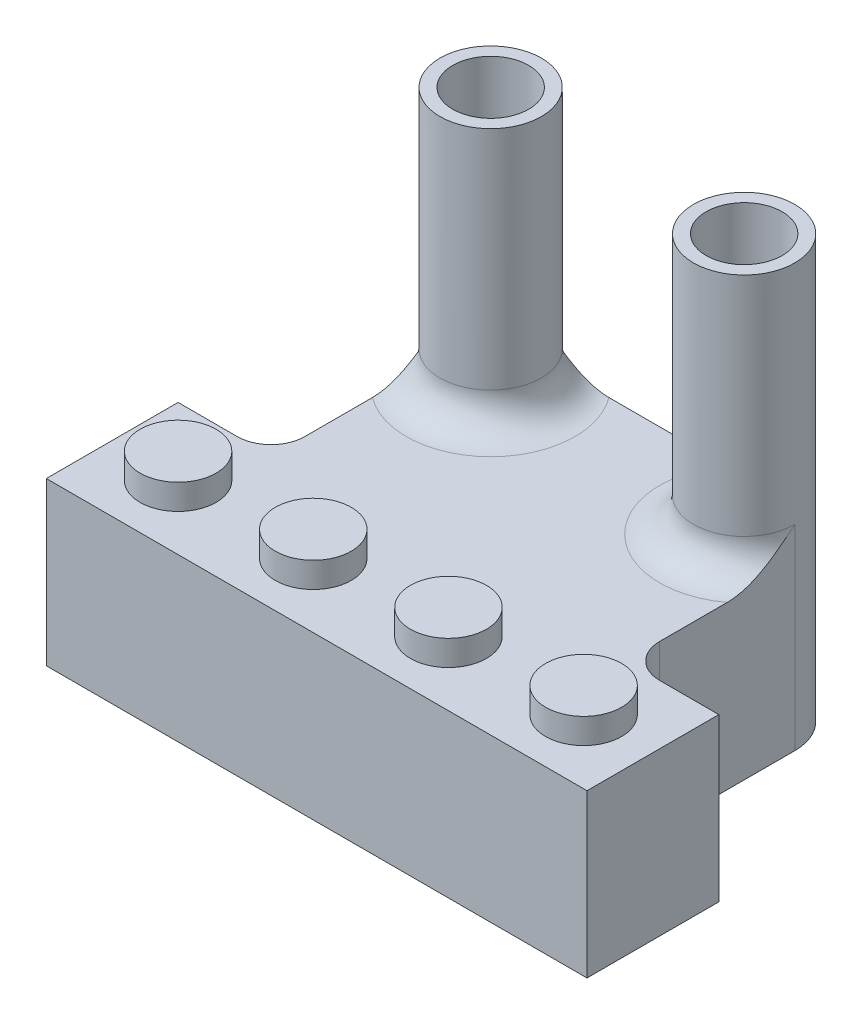
SolidWorks part; units mm, degrees
ref_plane "Front Plane" through (0, 0, 0) normal (0, 0, 1) x (1, 0, 0)
ref_plane "Top Plane" through (0, 0, 0) normal (0, 1, 0) x (1, 0, 0)
ref_plane "Right Plane" through (0, 0, 0) normal (1, 0, 0) x (0, 0, -1)
sketch "Sketch1" plane through (0, -0.3266, 0) normal (0, 1, 0) x (1, 0, 0)
  line L0 (236.8738, 42.5699) -> (268.8738, 42.5699)
  line L2 (236.8738, 50.3699) -> (236.8738, 42.5699)
  line L3 (236.8738, 50.3699) -> (268.8738, 50.3699)
  line L4 (268.8738, 34.3699) -> (268.8738, 50.3699)
  line L5 (268.8738, 50.3699) -> (236.8738, 50.3699)
  line L6 (236.8738, 50.3699) -> (236.8738, 34.3699)
  line L7 (236.8738, 34.3699) -> (268.8738, 34.3699)
  line L8 (268.8738, 34.3699) -> (268.8738, 50.3699) construction
  line L9 (268.8738, 50.3699) -> (236.8738, 50.3699) construction
  line L10 (236.8738, 50.3699) -> (236.8738, 34.3699) construction
  line L11 (236.8738, 34.3699) -> (268.8738, 34.3699) construction
  line L12 (268.8738, 50.3699) -> (268.8738, 42.5699)
  line L13 (242.3738, 50.3699) -> (242.3738, 61.3699)
  line L14 (244.3738, 63.3699) -> (261.3738, 63.3699)
  line L15 (263.3738, 61.3699) -> (263.3738, 50.3699)
  arc A0 (260.3738, 58.8199) -> (260.3738, 61.9199) centre (260.3738, 60.3699) ccw construction
  arc A1 (245.3738, 58.8199) -> (245.3738, 61.9199) centre (245.3738, 60.3699) ccw construction
  arc A2 (260.3738, 58.8199) -> (260.3738, 61.9199) centre (260.3738, 60.3699) ccw construction
  arc A3 (245.3738, 58.8199) -> (245.3738, 61.9199) centre (245.3738, 60.3699) ccw construction
  circle A12 centre (240.8738, 46.3699) radius 2.25
  circle A13 centre (248.8738, 46.3699) radius 2.25
  circle A14 centre (245.3738, 60.3699) radius 2.25
  circle A15 centre (260.3738, 60.3699) radius 2.25
  arc A16 (261.3738, 63.3699) -> (263.3738, 61.3699) centre (261.3738, 61.3699) cw
  arc A17 (242.3738, 61.3699) -> (244.3738, 63.3699) centre (244.3738, 61.3699) cw
  circle A18 centre (260.3738, 60.3699) radius 3
  circle A19 centre (245.3738, 60.3699) radius 3
  circle A20 centre (264.8738, 46.3699) radius 2.4 construction
  circle A21 centre (256.8738, 46.3699) radius 2.4 construction
  circle A22 centre (248.8738, 46.3699) radius 2.4 construction
  circle A23 centre (240.8738, 46.3699) radius 2.4 construction
  circle A24 centre (264.8738, 46.3699) radius 2.4 construction
  circle A25 centre (256.8738, 46.3699) radius 2.4 construction
  circle A26 centre (248.8738, 46.3699) radius 2.4 construction
  circle A27 centre (240.8738, 46.3699) radius 2.4 construction
  circle A28 centre (240.8738, 46.3699) radius 2.55
  circle A29 centre (248.8738, 46.3699) radius 2.55
  circle A30 centre (256.8738, 46.3699) radius 2.55
  circle A31 centre (264.8738, 46.3699) radius 2.55
  circle A32 centre (256.8738, 46.3699) radius 2.25
  circle A33 centre (264.8738, 46.3699) radius 2.25
  point P39 (252.8738, 63.3699)
  point P41 (252.8738, 50.3699)
  point P43 (263.3738, 63.3699)
  point P47 (242.3738, 63.3699)
  dimension "D3" = 0.15
  dimension "D4" = 0.15
  dimension "D5" = 4.5
  dimension "D8" = 2
  dimension "D2" = 7.8
  dimension "D6" = 21
  dimension "D7" = 13
  dimension "D10" = 32
  dimension "D1" = 0
extrude "Boss-Extrude1" add sketch "Sketch1" along normal blind 9.6 contours L0 L12 L3 L2
extrude "Cut-Extrude1" cut sketch "Sketch1<3>" along normal blind 1.7 contours A31 | A30 | A29 | A28
sketch "Sketch1<3>" plane through (0, -0.3266, 0) normal (0, 1, 0) x (1, 0, 0) same geometry as "Sketch1"
extrude "Boss-Extrude2" add sketch "Sketch1<4>" along normal blind 1.5 from surface contours A12 | A13 | A32 | A33 region at (240.8738, -0.3266, -46.3699) region at (248.8738, -0.3266, -46.3699) region at (256.8738, -0.3266, -46.3699) region at (264.8738, -0.3266, -46.3699) starting at face at (252.8738, 9.2734, -46.4699)
sketch "Sketch1<4>" plane through (0, -0.3266, 0) normal (0, 1, 0) x (1, 0, 0) same geometry as "Sketch1"
extrude "Boss-Extrude3" add sketch "Sketch1<5>" along normal up to surface (9.6 mm away) contours A17 L13 L3 L15 A16 L14 A15 A14 | A15 | A14 | L15 L13 L3 | A18 A15 | A14 region at (252.8738, -0.3266, -55.833) region at (258.3125, -0.3266, -58.3086) region at (245.3738, -0.3266, -60.3699) region at (260.3738, -0.3266, -60.3699) up to face at (240.8738, 9.2734, -44.1199)
sketch "Sketch1<5>" plane through (0, -0.3266, 0) normal (0, 1, 0) x (1, 0, 0) same geometry as "Sketch1"
extrude "Boss-Extrude4" add sketch "Sketch1<6>" along normal up to surface (25 mm away) contours A18 A15 | A19 A14 region at (243.3125, -0.3266, -62.4312) region at (258.3125, -0.3266, -58.3086)
sketch "Sketch1<6>" plane through (0, -0.3266, 0) normal (0, 1, 0) x (1, 0, 0) same geometry as "Sketch1"
fillet "Fillet1" radius 2 4 edges at (242.3738, 4.4734, -50.3699) (247.4952, 9.2734, -58.2486) (258.2525, 9.2734, -58.2486) (263.3738, 4.4734, -50.3699)
